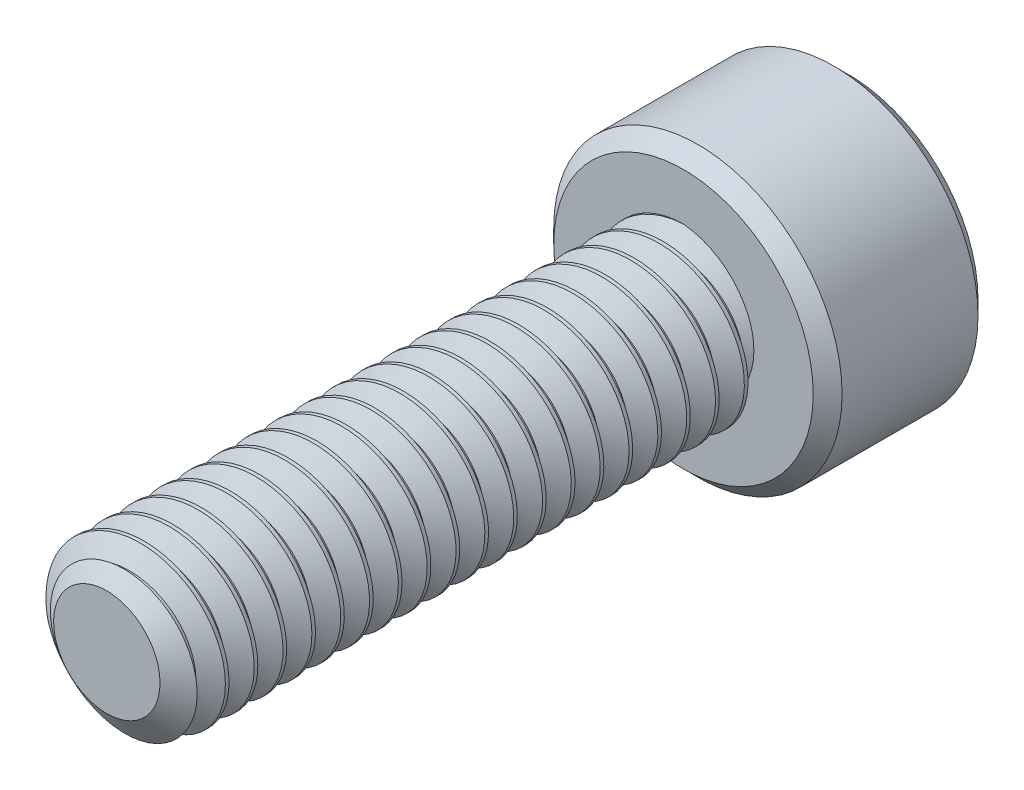
SolidWorks part; units mm, degrees
other "DetailItem1"
ref_plane "Front Plane" through (0, 0, 0) normal (0, 0, 1) x (1, 0, 0)
ref_plane "Top Plane" through (0, 0, 0) normal (0, 1, 0) x (1, 0, 0)
ref_plane "Right Plane" through (0, 0, 0) normal (1, 0, 0) x (0, 0, -1)
sketch "Sketch1" plane through (0, 0, 0) normal (0, 0, 1) x (1, 0, 0)
  circle A0 centre (0, 0) radius 2
  dimension "OD" = 4
extrude "Extrude1" add sketch "Sketch1" against normal blind 14
sketch "Sketch2" plane through (0, 0, 0) normal (0, 0, 1) x (1, 0, 0)
  circle A0 centre (0, 0) radius 2 construction
  circle A1 centre (0, 0) radius 2
curve "Helix/Spiral1" pitch 0.7 height 14.7 radius 2 centre (0, 0, 0) axis (0, 0, -1) start towards (0, 1, 0) parameters "pitch"=0.7
sketch "Sketch3" plane through (0, 0, 0) normal (1, 0, 0) x (0, 0, -1)
  line L0 (-0.6125, 2) -> (-0.35, 1.5453)
  line L1 (-0.35, 1.5453) -> (-0.2625, 1.5453)
  line L2 (-0.2625, 1.5453) -> (0, 2)
  line L3 (-0.6125, 2) -> (0, 2)
  line L4 (-0.3062, 2) -> (-0.3062, 1.5453) construction
  line L5 (-0.4812, 1.7727) -> (-0.1312, 1.7727) construction
  line L6 (0, 2) -> (0, -2) construction
  dimension "D1" = 0.0875
  dimension "D2" = 0.35
  dimension "D3" = 60
sweep "Cut-Sweep1" cut profiles "Sketch3" path "Helix/Spiral1" align with end faces yes
sketch "Sketch4" plane through (0, 0, 0) normal (1, 0, 0) x (0, 0, -1)
  line L0 (0.4962, 2) -> (0, 1.2913)
  line L1 (0, 1.2913) -> (0, 2)
  line L2 (0.4962, 2) -> (0, 2)
  line L3 (-0.6125, 2) -> (0, 2) construction
  line L4 (0, 0) -> (7.0209, 0) construction
  dimension "D1" = 55
  dimension "D2" = 0.254
revolve "Cut-Revolve1" cut sketch "Sketch4" angle 360 about L4
sketch "Sketch6" plane through (0, 0, -14) normal (0, 0, -1) x (-1, 0, 0)
  circle A0 centre (0, 0) radius 3.5
  dimension "head dia" = 7
extrude "Extrude2" add sketch "Sketch6" along normal blind 4
sketch "Sketch7" plane through (0, 0, -18) normal (0, 0, -1) x (-1, 0, 0)
  line L1 (0, 1.7321) -> (-1.5, 0.866)
  line L2 (-1.5, 0.866) -> (-1.5, -0.866)
  line L3 (-1.5, -0.866) -> (0, -1.7321)
  line L4 (0, -1.7321) -> (1.5, -0.866)
  line L5 (1.5, -0.866) -> (1.5, 0.866)
  line L6 (1.5, 0.866) -> (0, 1.7321)
  circle A0 centre (0, 0) radius 1.5 construction
  dimension "hex dia" = 3
extrude "Cut-Extrude1" cut sketch "Sketch7" against normal blind 2.25
sketch "Sketch8" plane through (0, 0, -18) normal (0, 0, -1) x (-1, 0, 0)
  circle A0 centre (0, 0) radius 1.7321
extrude "Cut-Extrude2" cut sketch "Sketch8" against normal through all draft 45
chamfer "Chamfer1" distance 0.35 angle 45 2 edges at (-3.5, 0, -18) (-3.5, 0, -14)
sketch "Sketch10" plane through (0, 0, -14) normal (0, 0, 1) x (1, 0, 0)
  circle A1 centre (0, 0) radius 2
  circle A2 centre (0, 0) radius 2
  dimension "D1" = 0
ref_plane "Plane1" through (0, 0, 0) normal (0, 0, 1) x (1, 0, 0)
extrude "partial thread" [suppressed] add sketch "Sketch10" along normal up to surface (10 mm away) separate body up to plane "Plane1"
chamfer "Chamfer2" [suppressed] distance 0.08 angle 45
combine bodies "Combine1" [suppressed] operation type add bodies to combine 107 108
sketch "Sketch9" plane through (0, 0, 0) normal (1, 0, 0) x (0, 0, -1)
  line L0 (0, 2) -> (0, -2) construction
  line L1 (1.75, 2) -> (1.75, -2) construction
  dimension "D1" = 1.75
equation "\"D3@Helix/Spiral1\" = \"screw length@Extrude1\"+\"pitch@Helix/Spiral1\""
equation "\"D1@Sketch3\" = \"pitch@Helix/Spiral1\"*.125"
equation "\"D2@Sketch3\" = \"pitch@Helix/Spiral1\"*.5"
equation "\"D1@Cut-Extrude1\" = \"hex dia@Sketch7\"*.75"
equation "\"D1@Chamfer1\" = \"head dia@Sketch6\"*.05"
equation "\"D1@Sketch9\" = \"pitch@Helix/Spiral1\"*2.5"
equation "\"D1@Chamfer2\"=\"OD@Sketch1\"*.02"
